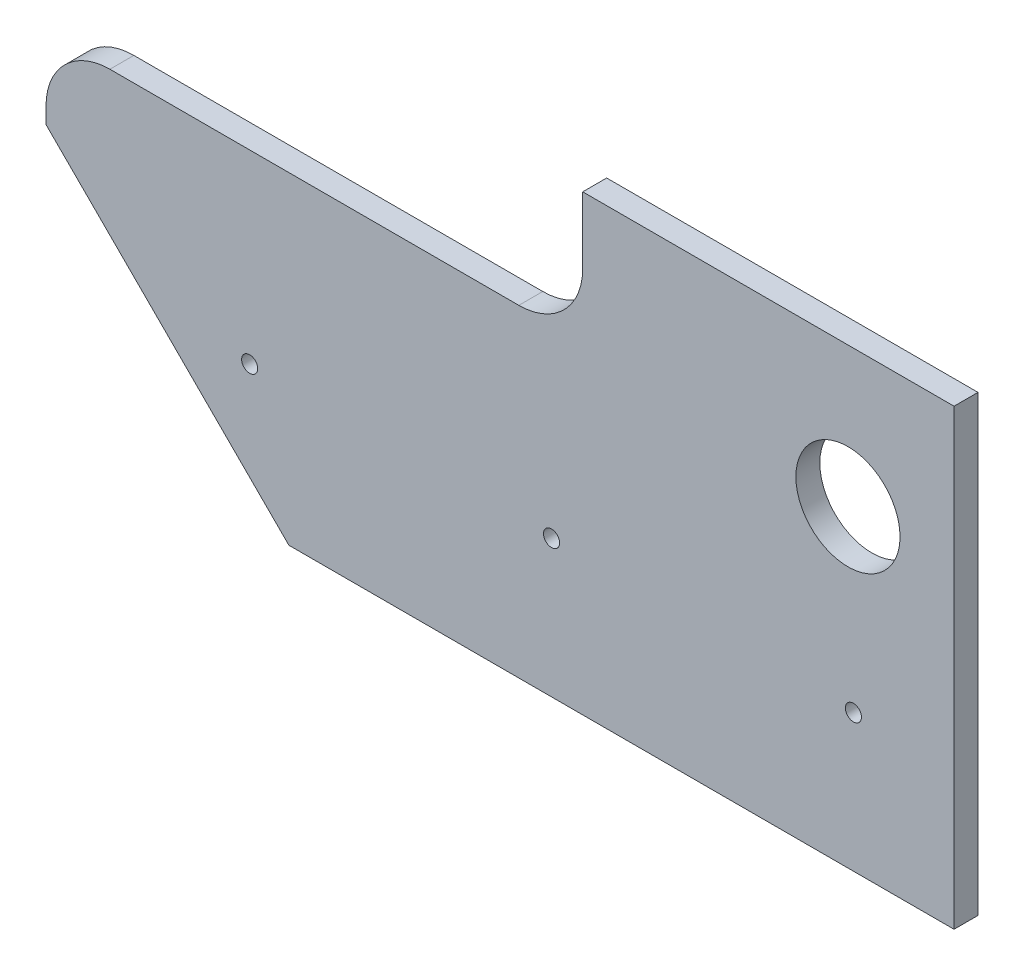
SolidWorks part; units mm, degrees
ref_plane "Front Plane" through (0, 0, 0) normal (0, 0, 1) x (1, 0, 0)
ref_plane "Top Plane" through (0, 0, 0) normal (0, 1, 0) x (1, 0, 0)
ref_plane "Right Plane" through (0, 0, 0) normal (1, 0, 0) x (0, 0, -1)
sketch "Sketch1" plane through (0, 0, 0) normal (0, 0, 1) x (1, 0, 0)
  line L0 (-138.2594, 48.9915) -> (32.2106, -121.4785)
  line L1 (32.2106, -121.4785) -> (222.7106, -121.4785)
  line L2 (-138.2594, 146.2068) -> (-138.2594, 48.9915)
  line L3 (-138.2594, 146.2068) -> (222.7106, 146.2068)
  line L4 (222.7106, -121.4785) -> (222.7106, 146.2068)
  circle A0 centre (180.538, 76.832) radius 20.701
  circle A2 centre (180.538, 76.832) radius 69.85 construction
  circle A3 centre (180.538, 76.832) radius 318.7974 construction
  point P0 (0, 0)
  point P2 (180.538, 76.832)
  dimension "D4" = 198.3105
  dimension "D1" = 45
  dimension "D2" = 267.6854
  dimension "D5" = 245.11
extrude "Boss-Extrude1" add sketch "Sketch1" along normal blind 9.525
sketch "Sketch2" plane through (0, 0, 9.525) normal (0, 0, 1) x (1, 0, 0)
  line L0 (32.2106, -121.4785) -> (222.7106, -121.4785) construction
  line L1 (241.7606, -121.4785) -> (-43.8123, -121.4785)
  line L2 (241.7606, -121.4785) -> (241.7606, -47.5645)
  line L3 (241.7606, -47.5645) -> (-43.8123, -47.5645)
  line L4 (-43.8123, -121.4785) -> (-43.8123, -47.5645)
extrude "Cut-Extrude1" cut sketch "Sketch2" against normal through all contours L3 L4 L1 L2
sketch "Sketch4" plane through (0, 0, 9.525) normal (0, 0, 1) x (1, 0, 0)
  line L1 (-138.2594, 146.2068) -> (-138.2594, 48.9915) construction
  line L3 (-138.2594, 146.2068) -> (75.1006, 146.2068)
  line L4 (-138.2594, 146.2068) -> (-138.2594, 80.7415)
  line L5 (-138.2594, 80.7415) -> (75.1006, 80.7415)
  line L6 (75.1006, 146.2068) -> (75.1006, 80.7415)
extrude "Cut-Extrude2" cut sketch "Sketch4" against normal through all contours L5 L6 L3 L4
fillet "Fillet2" radius 25.4 2 edges at (-138.2594, 80.7415, 4.7625) (75.1006, 80.7415, 4.7625)
hole_wizard "Ø6.4 (6.4) Diameter Hole2" positions "Sketch15" profile "Sketch14" hole size "Ø6.4" standard "Lanco STD" end condition through all
sketch "Sketch15" plane through (0, 0, 0) normal (0, 0, -1) x (-1, 0, 0)
  line L2 (-222.7106, -47.5645) -> (-222.7106, 146.2068) construction
  point P3 (-182.7106, 7.0429)
  point P6 (-62.7106, 7.0429)
  point P9 (57.2894, 7.0429)
  dimension "D1" = 40
  dimension "D2" = 120
  dimension "D3" = 120
sketch "Sketch14" plane through (182.7106, 7.0429, 0) normal (1, 0, 0) x (0, 1, 0)
  line L0 (0, 0) -> (0, 9.525)
  line L1 (0, 9.525) -> (3.2, 9.525)
  line L2 (3.2, 9.525) -> (3.2, 0)
  line L5 (3.2, 0) -> (0, 0)
  line L11 (0, -6.35) -> (0, 107.95) construction
  dimension "Thru Hole Dia." = 6.4
  dimension "Thru Hole Depth" = 9.525
sketch "Sketch16" plane through (222.7106, 0, 0) normal (1, 0, 0) x (0, 0, -1)
  line L0 (0, -47.5645) -> (0, 146.2068) construction
  line L1 (-9.525, 146.2068) -> (0, 146.2068)
  line L2 (-9.525, 146.2068) -> (-9.525, 145.2215)
  line L3 (-9.525, 145.2215) -> (0, 145.2215)
  line L4 (0, 146.2068) -> (0, 145.2215)
extrude "Cut-Extrude3" cut sketch "Sketch16" against normal through all
sketch "Sketch17" plane through (0, 0, 0) normal (0, 0, -1) x (-1, 0, 0)
  line L0 (-222.7106, -47.5645) -> (-222.7106, 145.2215) construction
  line L1 (-75.1006, 145.2215) -> (-222.7106, 145.2215)
  line L2 (-75.1006, 145.2215) -> (-75.1006, 132.5215)
  line L3 (-75.1006, 132.5215) -> (-222.7106, 132.5215)
  line L4 (-222.7106, 145.2215) -> (-222.7106, 132.5215)
  dimension "D1" = 12.7
extrude "Cut-Extrude4" cut sketch "Sketch17" against normal through all
